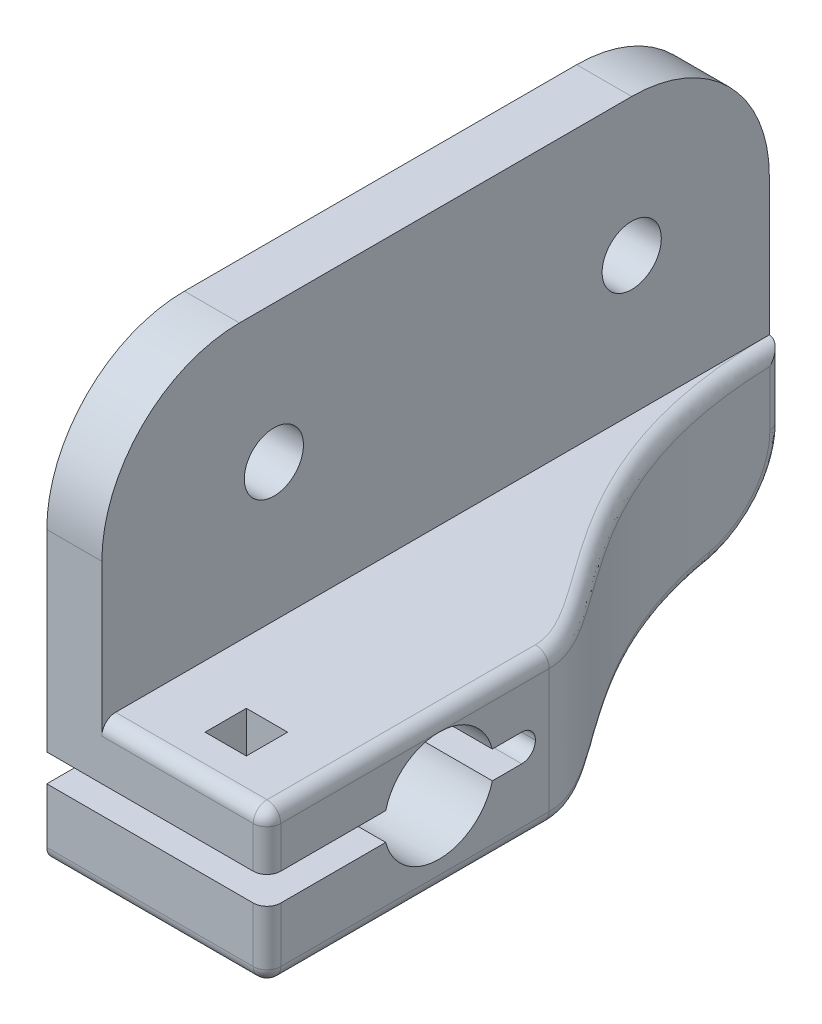
SolidWorks part; units mm, degrees
ref_plane "Plan de face" through (0, 0, 0) normal (0, 0, 1) x (1, 0, 0)
ref_plane "Plan de dessus" through (0, 0, 0) normal (0, 1, 0) x (1, 0, 0)
ref_plane "Plan de droite" through (0, 0, 0) normal (1, 0, 0) x (0, 0, -1)
sketch "Esquisse1" plane through (0, 0, 0) normal (0, 0, 1) x (1, 0, 0)
  line L1 (-288, -11) -> (-272, -11)
  line L2 (-284, 0) -> (-284, 20)
  line L3 (-284, 20) -> (-288, 20)
  line L4 (-288, 20) -> (-288, 0)
  line L8 (-288, 0) -> (-288, -11)
  line L10 (-272, -11) -> (-272, 0)
  line L11 (-272, 0) -> (-284, 0)
  dimension "D7" = 11
  dimension "D2" = 20
  dimension "D3" = 12
  dimension "D4" = 4
extrude "Boss.-Extru.1" add sketch "Esquisse1" along normal blind 25
hole_wizard "Dégagement M41" positions "Esquisse3" profile "Esquisse2" hole size "M4" standard "Din"
sketch "Esquisse3" plane through (-288, 0, 0) normal (-1, 0, 0) x (0, 0, 1)
  line L0 (25, 20) -> (0, 20) construction
  line L2 (12.5, 10) -> (12.5, 20) construction
  point P0 (12.5, 10)
  dimension "D1" = 10
sketch "Esquisse2" plane through (-288, 10, 12.5) normal (0, 1, 0) x (0, 0, 1)
  line L0 (0, 0) -> (0, 5)
  line L1 (0, 5) -> (2.15, 5)
  line L2 (2.15, 5) -> (2.15, 0)
  line L5 (2.15, 0) -> (0, 0)
  line L10 (0, 5) -> (-2.15, 5) construction
  line L11 (0, -6.35) -> (0, 107.95) construction
  dimension "Diamètre du perçage" = 4.3
  dimension "Profondeur du perçage" = 5
  dimension "Angle de pointe" = 180
sketch "Esquisse4" plane through (-272, 0, 0) normal (-1, 0, 0) x (0, 0, 1)
  line L0 (25, 0) -> (0, 0) construction
  line L1 (25, -4) -> (16.373, -4)
  line L2 (25, -4) -> (25, -6)
  line L3 (25, -6) -> (16.373, -6)
  line L4 (5.5, -4.99) -> (5.5, -5.01)
  line L6 (25, -11) -> (0, -11) construction
  line L7 (8.627, -6) -> (6.49, -6)
  line L8 (8.627, -4) -> (6.49, -4)
  line L9 (25, 20) -> (25, -11) construction
  line L12 (0, -5) -> (12.5, -5) construction
  arc A0 (8.627, -6) -> (16.373, -6) centre (12.5, -5) ccw
  arc A1 (6.49, -6) -> (5.5, -5.01) centre (6.49, -5.01) cw
  arc A2 (6.49, -4) -> (5.5, -4.99) centre (6.49, -4.99) ccw
  arc A3 (16.373, -4) -> (8.627, -4) centre (12.5, -5) ccw
  point P16 (5.5, -4)
  dimension "D4" = 8
  dimension "D6" = 0.99
  dimension "D7" = 0.99
  dimension "D1" = 19.5
  dimension "D2" = 2
  dimension "D3" = 1
  dimension "D5" = 12.5
  dimension "D8" = 5
  dimension "D9" = 6
extrude "Enlèv. mat.-Extru.1" cut sketch "Esquisse4" along normal through all
sketch "Esquisse5" plane through (0, -11, 0) normal (0, 1, 0) x (1, 0, 0)
  line L1 (-279.5, -19) -> (-276.5, -19)
  line L2 (-279.5, -19) -> (-279.5, -22)
  line L3 (-279.5, -22) -> (-276.5, -22)
  line L4 (-276.5, -19) -> (-276.5, -22)
  line L5 (-278, -22) -> (-278, -25) construction
  line L7 (-272, -25) -> (-284, -25) construction
  dimension "D1" = 3
  dimension "D2" = 3
extrude "Enlèv. mat.-Extru.2" cut sketch "Esquisse5" along normal through all
sketch "Esquisse6" plane through (0, 0, 0) normal (0, 0, -1) x (-1, 0, 0)
  line L23 (288, -11) -> (288, 20)
  line L24 (288, 20) -> (284, 20)
  line L25 (284, 20) -> (284, 0)
  line L26 (284, 0) -> (272, 0)
  line L27 (272, 0) -> (272, -11)
  line L28 (272, -11) -> (288, -11)
  line L33 (288, -11) -> (288, 20)
  line L34 (288, 20) -> (284, 20)
  line L35 (284, 20) -> (284, 0)
  line L36 (284, 0) -> (272, 0)
  line L37 (272, 0) -> (272, -11)
  line L38 (272, -11) -> (288, -11)
  dimension "D1" = 0
extrude "Boss.-Extru.2" add sketch "Esquisse6" along normal up to surface (23.5 mm away)
fillet "Congé2" radius 6 1 edges at (-280, -11, -23.5) tangent propagation no
fillet "Congé3" radius 10 2 edges at (-286, 20, 25) (-286, 20, -23.5)
fillet "Congé4" radius 1 2 edges at (-278, 0, 25) (-280, -11, 25)
hole_wizard "Dégagement M42" positions "Esquisse8" profile "Esquisse7" hole size "M4" standard "Din"
sketch "Esquisse8" plane through (-284, 0, 0) normal (1, 0, 0) x (0, 0, -1)
  line L0 (13.5, 10) -> (-12.5, 10) construction
  line L1 (23.5, 0) -> (23.5, 10) construction
  point P0 (13.5, 10)
  dimension "D1" = 10
sketch "Esquisse7" plane through (-284, 10, -13.5) normal (0, 1, 0) x (0, 0, -1)
  line L0 (0, 0) -> (0, 5)
  line L1 (0, 5) -> (2.15, 5)
  line L2 (2.15, 5) -> (2.15, 0)
  line L5 (2.15, 0) -> (0, 0)
  line L10 (0, 5) -> (-2.15, 5) construction
  line L11 (0, -6.35) -> (0, 107.95) construction
  dimension "Diamètre du perçage" = 4.3
  dimension "Profondeur du perçage" = 5
  dimension "Angle de pointe" = 180
sketch "Esquisse9" plane through (0, 0, 0) normal (0, 1, 0) x (1, 0, 0)
  line L0 (-272, -24) -> (-272, 23.5) construction
  line L1 (-272, 23.5) -> (-284, 23.5) construction
  line L2 (-284, 13.5) -> (-284, 23.5) construction
  line L3 (-288, -5.5) -> (-272, -5.5) construction
  line L4 (-283, -370.1509) -> (-283, -334.3738) construction
  line L5 (-272, -359.718) -> (-272, -353.7892) construction
  line L6 (-283, 23.5) -> (-272, 23.5)
  line L7 (-272, 23.5) -> (-272, -4.5)
  spline S0 degree 3 poles (-272, -4.5) (-272, 0.7315) (-283, 6.7467) (-283, 23.5) knots 0 0 0 0 1 1 1 1
  dimension "D1" = 1
  dimension "D2" = 1
extrude "Enlèv. mat.-Extru.3" cut sketch "Esquisse9" against normal through all
fillet "Congé5" radius 1 10 edges at (-272, -8, 25) (-272, -10.7071, 24.7071) (-272, -11, 14.25) (-282.9301, -9.7086, -21.2187) (-283, -2.5, -23.5) (-272, -2.5, 25) (-272, -0.2929, 24.7071) (-272, 0, 14.25)
move or copy body "Corps-Déplacer/Copier1" [suppressed] bodies to move or copy 104
